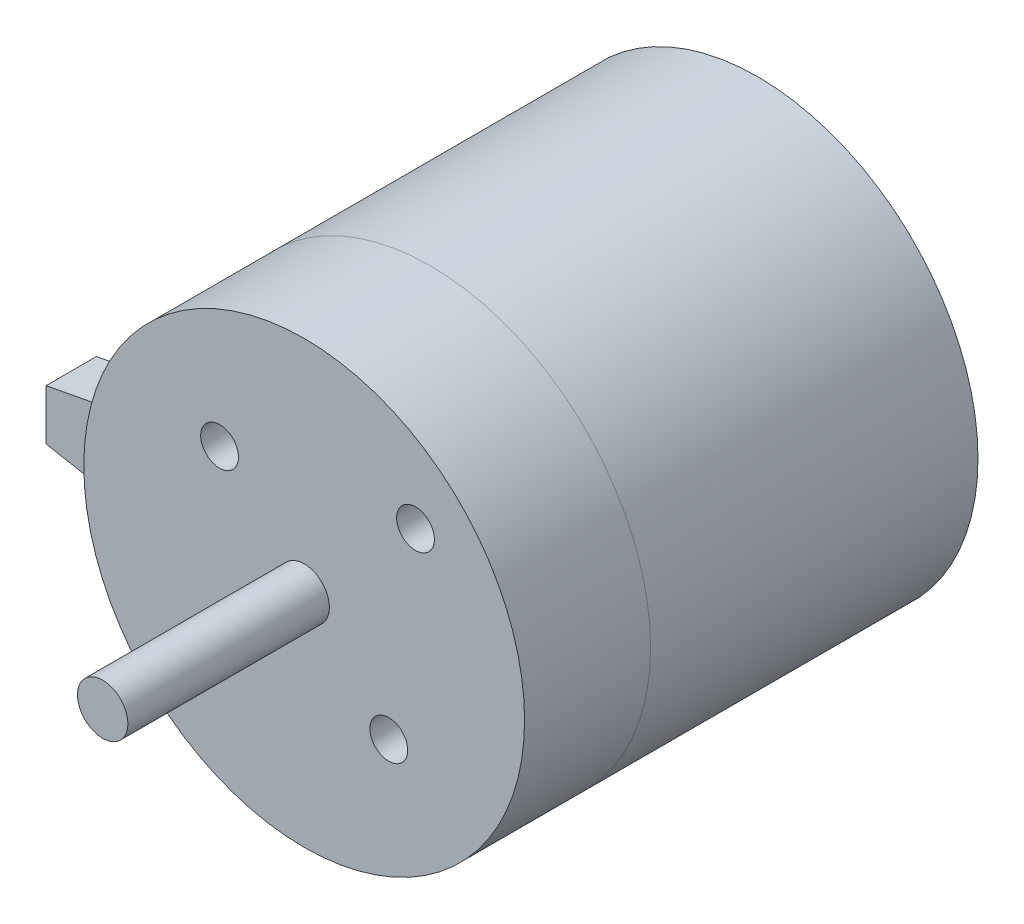
SolidWorks part; units mm, degrees
ref_plane "Front Plane" through (0, 0, 0) normal (0, 0, 1) x (1, 0, 0)
ref_plane "Top Plane" through (0, 0, 0) normal (0, 1, 0) x (1, 0, 0)
ref_plane "Right Plane" through (0, 0, 0) normal (1, 0, 0) x (0, 0, -1)
sketch "Base" plane through (0, 0, 0) normal (0, 0, 1) x (1, 0, 0)
  line L0 (0, 14.02) -> (0, -11.8422) construction
  line L1 (-31.0348, 0) -> (14.0598, 0) construction
  line L2 (-8.8388, -8.8388) -> (8.8388, 8.8388) construction
  line L3 (-6.7175, 6.7175) -> (6.7175, -6.7175) construction
  line L4 (-17.2409, 3) -> (-22.5, 2)
  line L5 (-22.5, 2) -> (-22.5, -2)
  line L6 (-17.2409, -3) -> (-22.5, -2)
  circle A0 centre (0, 0) radius 17.5
  circle A1 centre (0, 0) radius 5.5
  circle A2 centre (0, 0) radius 7.5 construction
  circle A3 centre (0, 7.5) radius 1.25
  circle A4 centre (6.4952, -3.75) radius 1.25
  circle A5 centre (-6.4952, -3.75) radius 1.25
  circle A6 centre (0, 0) radius 2
  circle A7 centre (0, 0) radius 12.5 construction
  circle A8 centre (0, 0) radius 9.5 construction
  circle A9 centre (8.8388, 8.8388) radius 1.5
  circle A10 centre (-8.8388, -8.8388) radius 1.5
  circle A11 centre (6.7175, -6.7175) radius 1.5
  circle A12 centre (-6.7175, 6.7175) radius 1.5
  point P17 (0, 0)
  point P31 (-22.5, 0)
  dimension "D1" = 35
  dimension "D2" = 11
  dimension "D3" = 15
  dimension "D4" = 2.5
  dimension "D6" = 4
  dimension "D7" = 25
  dimension "D8" = 19
  dimension "D11" = 3
  dimension "D12" = 3
  dimension "D13" = 3
  dimension "D14" = 3
  dimension "D9" = 45
  dimension "D10" = 90
  dimension "D15" = 5
  dimension "D16" = 3
  dimension "D17" = 2
  dimension "D5" = 3
sketch "Sketch3" plane through (0, 0, 0) normal (0, 0, 1) x (1, 0, 0)
  line L0 (0, 14.02) -> (0, -11.8422) construction
  line L1 (-11.4424, 0) -> (14.0598, 0) construction
  circle A0 centre (0, 0) radius 17.5
  circle A1 centre (0, 0) radius 5.5
  circle A2 centre (0, 0) radius 7.5 construction
  circle A3 centre (0, 7.5) radius 1.25
  circle A4 centre (6.4952, -3.75) radius 1.25
  circle A5 centre (-6.4952, -3.75) radius 1.25
  circle A6 centre (0, 0) radius 2
  point P17 (0, 0)
  dimension "D1" = 35
  dimension "D2" = 11
  dimension "D3" = 15
  dimension "D4" = 2.5
  dimension "D6" = 4
  dimension "D5" = 3
extrude "Boss-Extrude2" add sketch "Sketch3" along normal blind 36 contours A0 A5 A4 A3 A1 | A3 | A1 A6 | A6 | A5 | A4 region at (-17.005, 0, 0) region at (-5.3444, 0, 0) region at (0, 7.5, 0) region at (6.4952, -3.75, 0) region at (-6.4952, -3.75, 0) region at (0, 0, 0)
extrude "Boss-Extrude3" add sketch "Sketch3<4>" along normal blind 16 from surface contours A6 region at (0, 0, 0) starting at face at (17.5, 0, 36)
sketch "Sketch3<4>" plane through (0, 0, 0) normal (0, 0, 1) x (1, 0, 0) same geometry as "Sketch3"
extrude "Boss-Extrude4" add sketch "Sketch3<5>" against normal blind 2 contours A1 A6 region at (-5.3444, 0, 0)
sketch "Sketch3<5>" plane through (0, 0, 0) normal (0, 0, 1) x (1, 0, 0) same geometry as "Sketch3"
extrude "Cut-Extrude1" cut sketch "Sketch3<8>" along normal blind 3.5 contours A3 | A4 | A5 region at (0, 7.5, 0) region at (6.4952, -3.75, 0) region at (-6.4952, -3.75, 0)
sketch "Sketch3<8>" plane through (0, 0, 0) normal (0, 0, 1) x (1, 0, 0) same geometry as "Sketch3"
extrude "Cut-Extrude2" cut sketch "Base" against normal blind 3 from surface contours A9 | A12 | A10 | A11 region at (8.8388, 8.8388, 0) region at (-8.8388, -8.8388, 0) region at (6.7175, -6.7175, 0) region at (-6.7175, 6.7175, 0) starting at face at (2, 0, 36)
extrude "Boss-Extrude5" add sketch "Base<4>" against normal blind 4 from offset 34 contours A0 L4 L5 L6 region at (-19.7917, 0, 0)
sketch "Base<4>" plane through (0, 0, 0) normal (0, 0, 1) x (1, 0, 0) same geometry as "Base"
ref_plane "BaseOffset" through (0, 0, 26) normal (0, 0, 1) x (1, 0, 0)
split line "Split Line2"
equation "\"TrackerMass\"= 100'judges tracker mass"
equation "\"CargoMass\"= 250'mass of cargo"
equation "\"X2814MotorDiameter\"= 35mm'Outer diameter of X2814 motor"
equation "\"X2814MotorLength\"= 36mm'X2814 Motor lenght"
equation "\"X2814PadHeight\"= 2mm"
equation "\"X2814ShaftDiameter\"= 4mm"
equation "\"X2814ShaftLength\"= 16mm"
equation "\"X2814PadDiameter\"= 11mm"
equation "\"X2814PadHoleCircleDiameter\"= 15mm"
equation "\"X2814PadScrewDiameter\"= 2.5mm"
equation "\"X2814WireLength\"= 110mm"
equation "\"X2814ShaftHoleLargeCircleDiameter\"= 25mm"
equation "\"X2814ShaftHoleSmallCircleDiameter\"= 19mm"
equation "\"X2814ShaftScrewDiameter\"= 3mm"
equation "\"D1@Base\" = \"X2814MotorDiameter\""
equation "\"D2@Base\" = \"X2814PadDiameter\""
equation "\"D3@Base\" = \"X2814PadHoleCircleDiameter\""
equation "\"D4@Base\" = \"X2814PadScrewDiameter\""
equation "\"D6@Base\" = \"X2814ShaftDiameter\""
equation "\"D1@Boss-Extrude2\"=\"X2814MotorLength\""
equation "\"D1@Boss-Extrude3\"=\"X2814ShaftLength\""
equation "\"D1@Boss-Extrude4\"=\"X2814PadHeight\""
equation "\"X2814PadScrewDepth\"= 3.5mm"
equation "\"X2814ShaftScrewDepth\"= 3mm"
equation "\"D1@Cut-Extrude1\"=\"X2814PadScrewDepth\""
equation "\"D7@Base\"=\"X2814ShaftHoleLargeCircleDiameter\""
equation "\"D8@Base\"=\"X2814ShaftHoleSmallCircleDiameter\""
equation "\"D11@Base\"=\"X2814ShaftScrewDiameter\""
equation "\"D12@Base\"=\"D11@Base\""
equation "\"D13@Base\"=\"D11@Base\""
equation "\"D14@Base\"=\"D11@Base\""
equation "\"D1@Cut-Extrude2\"=\"X2814ShaftScrewDepth\""
equation "\"D19@Boss-Extrude5\"=\"X2814MotorLength\"-2"
equation "\"X2814BaseOffset\"= 10mm"
equation "\"D1@BaseOffset\"=\"X2814BaseOffset\""
